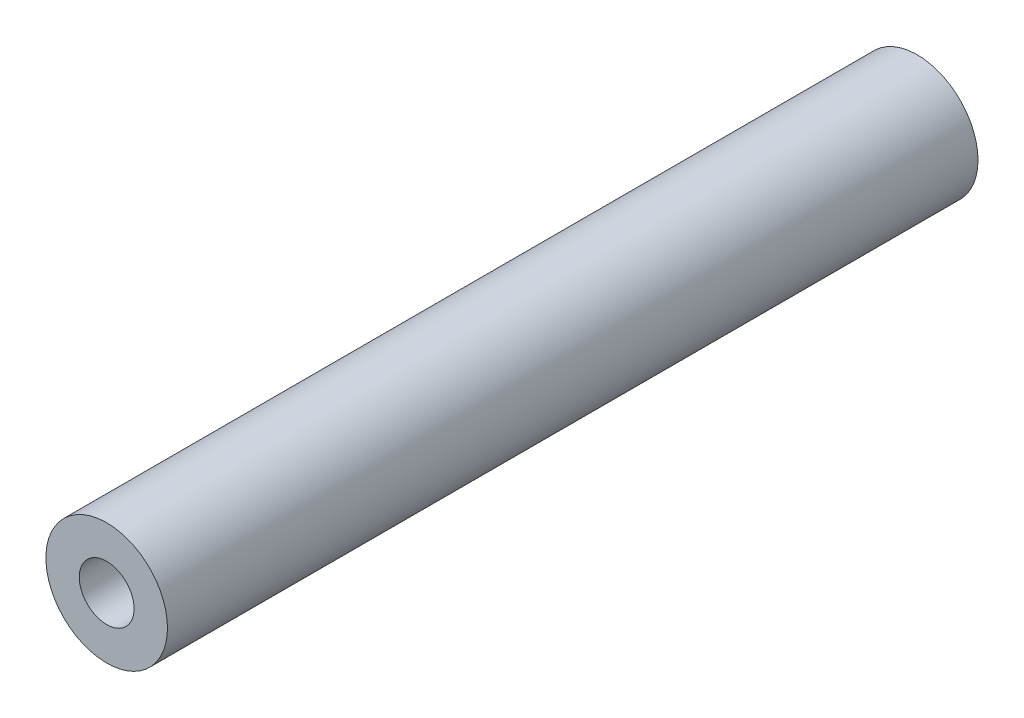
SolidWorks part; units mm, degrees
material "Alloy Steel"
ref_plane "Front Plane" through (0, 0, 0) normal (0, 0, 1) x (1, 0, 0)
ref_plane "Top Plane" through (0, 0, 0) normal (0, 1, 0) x (1, 0, 0)
ref_plane "Right Plane" through (0, 0, 0) normal (1, 0, 0) x (0, 0, -1)
sketch "Sketch1" plane through (0, 0, 0) normal (0, 0, 1) x (1, 0, 0)
  circle A0 centre (0, 0) radius 3
  dimension "D1" = 6
extrude "Boss-Extrude1" add sketch "Sketch1" along normal blind 40
ref_axis "Axis1" through (0, 0, 40) along (0, 0, -1)
hole_wizard "#6-32 Tapped Hole1" positions "Sketch2" profile "Sketch3" tap size "#6-32" standard "ANSI Inch"
sketch "Sketch2" plane through (0, 0, 0) normal (0, 0, -1) x (-1, 0, 0)
  point P0 (0, 0)
cosmetic thread "Hole Thread1" parameters "D1"=12, "D2"=3.5052
sketch "Sketch3" plane through (0, 0, 0) normal (1, 0, 0) x (0, 1, 0)
  line L0 (0, 0) -> (0, 12.8127)
  line L1 (0, 12.8127) -> (1.3525, 12)
  line L2 (1.3525, 12) -> (1.3525, 0)
  line L5 (1.3525, 0) -> (0, 0)
  line L10 (0, 12.8127) -> (-1.3526, 12) construction
  line L11 (0, -6.35) -> (0, 107.95) construction
  dimension "Tap Drill Dia." = 2.7051
  dimension "Tap Drill Depth" = 12
  dimension "Drill Angle" = 118
hole_wizard "#6-32 Tapped Hole2" positions "Sketch4" profile "Sketch5" tap size "#6-32" standard "ANSI Inch"
sketch "Sketch4" plane through (0, 0, 40) normal (0, 0, 1) x (1, 0, 0)
  point P0 (0, 0)
sketch "Sketch5" plane through (0, 0, 40) normal (1, 0, 0) x (0, -1, 0)
  line L0 (0, 0) -> (0, 12.8127)
  line L1 (0, 12.8127) -> (1.3525, 12)
  line L2 (1.3525, 12) -> (1.3525, 0)
  line L5 (1.3525, 0) -> (0, 0)
  line L10 (0, 12.8127) -> (-1.3526, 12) construction
  line L11 (0, -6.35) -> (0, 107.95) construction
  dimension "Tap Drill Dia." = 2.7051
  dimension "Tap Drill Depth" = 12
  dimension "Drill Angle" = 118
cosmetic thread "Hole Thread2" parameters "D1"=12, "D2"=3.5052
